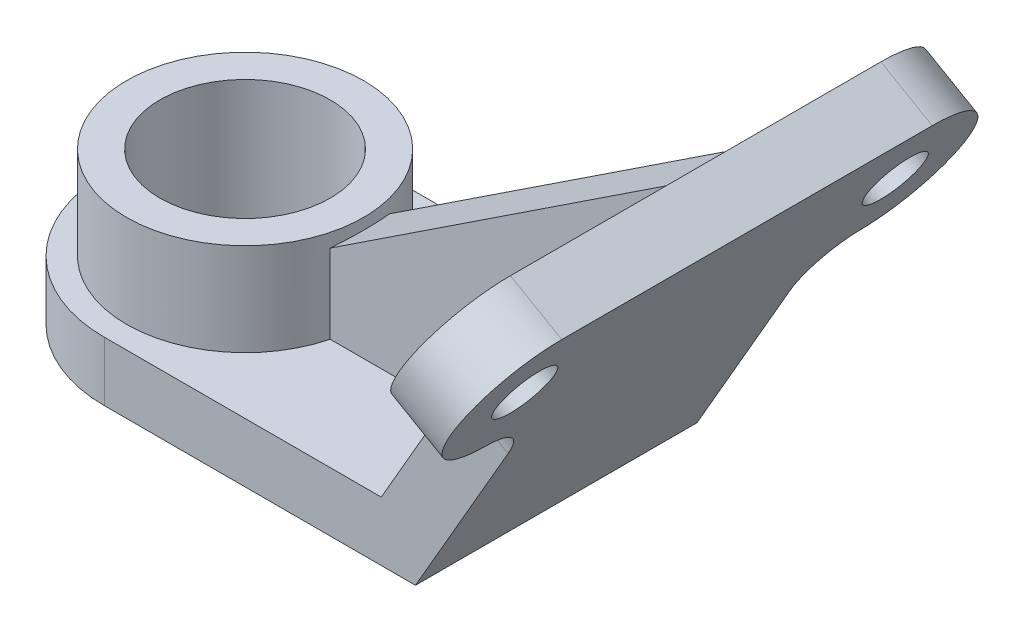
SolidWorks part; units mm, degrees
ref_plane "前视基准面" through (0, 0, 0) normal (0, 0, 1) x (1, 0, 0)
ref_plane "上视基准面" through (0, 0, 0) normal (0, 1, 0) x (1, 0, 0)
ref_plane "右视基准面" through (0, 0, 0) normal (1, 0, 0) x (0, 0, -1)
other "Configuration Table"
sketch "草图1" plane through (0, 0, 0) normal (0, 1, 0) x (1, 0, 0)
  line L0 (0, 38) -> (84, 38)
  line L1 (84, 38) -> (84, -38)
  line L2 (84, -38) -> (0, -38)
  circle A0 centre (0, 0) radius 23
  circle A1 centre (0, 0) radius 32
  arc A2 (0, 38) -> (0, -38) centre (0, 0) ccw
  dimension "D1" = 76
  dimension "D2" = 64
  dimension "D3" = 46
  dimension "D4" = 84
extrude "凸台-拉伸1" add sketch "草图1" along normal blind 16 contours L0 A2 L2 L1 A1 region at (42.601, 0, 0)
extrude "凸台-拉伸2" add sketch "草图1<3>" along normal blind 41 contours A1 A0 region at (-31.0949, 0, 0)
sketch "草图1<3>" plane through (0, 0, 0) normal (0, 1, 0) x (1, 0, 0) same geometry as "草图1"
ref_plane "基准面2" through (63, -36.3731, 0) normal (-0.866, 0.5, 0) x (0, 0, 1)
sketch "草图3" plane through (63, -36.3731, 0) normal (-0.866, 0.5, 0) x (0, 0, 1)
  line L0 (-38, 42) -> (-38, 92)
  line L1 (-51, 105) -> (-50, 105)
  line L2 (-38, 42) -> (38, 42)
  line L3 (-50, 145) -> (50, 145)
  line L4 (0, 0) -> (0, 232.6487) construction
  line L6 (51, 105) -> (50, 105)
  line L7 (38, 42) -> (38, 92)
  line L9 (-38, 42) -> (38, 42) construction
  arc A0 (-38, 92) -> (-51, 105) centre (-51, 92) ccw
  arc A1 (-50, 145) -> (-50, 105) centre (-50, 125) ccw
  circle A2 centre (-50, 125) radius 8
  circle A3 centre (50, 125) radius 8
  arc A4 (50, 145) -> (50, 105) centre (50, 125) cw
  arc A5 (38, 92) -> (51, 105) centre (51, 92) cw
  point P23 (0, 145)
  point P24 (0, 55.8564)
  dimension "D1" = 13
  dimension "D2" = 16
  dimension "D3" = 100
  dimension "D4" = 103
  dimension "D5" = 20
extrude "凸台-拉伸3" add sketch "草图3" along normal blind 16
sketch "草图4" plane through (0, 0, 0) normal (0, 0, 1) x (1, 0, 0)
  line L0 (121.6436, 97.2006) -> (32, 38)
  line L1 (32, 16) -> (32, 41) construction
  line L2 (74.7624, 16) -> (0, 16) construction
  dimension "D1" = 22
rib "筋1" sketch "草图4" sketch "草图4" thickness 16 extrusion direction parallel to sketch draft on no parameters "D1"=16
